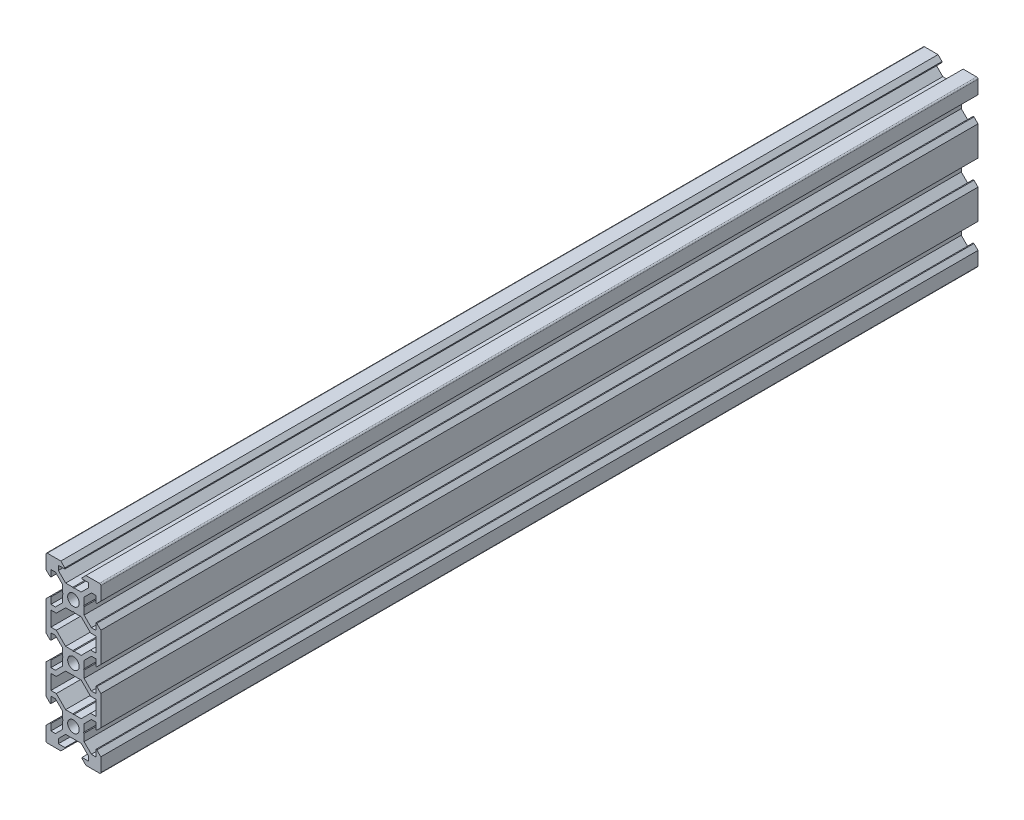
SolidWorks part; units mm, degrees
ref_plane "Plan de face" through (0, 0, 0) normal (0, 0, 1) x (1, 0, 0)
ref_plane "Plan de dessus" through (0, 0, 0) normal (0, 1, 0) x (1, 0, 0)
ref_plane "Plan de droite" through (0, 0, 0) normal (1, 0, 0) x (0, 0, -1)
ref_axis "Axe" through (0, 0, -13.782) along (0, 0, 1)
sketch "Esquisse1" plane through (0, 0, 0) normal (0, 0, 1) x (1, 0, 0)
  line L0 (0, 27.6392) -> (0, -27.6392) construction
  line L1 (-33.6074, 0) -> (33.6074, 0) construction
  line L2 (0, 0) -> (-22.2114, 22.2114) construction
  line L3 (-9.5, 10) -> (-4.58, 10)
  line L4 (-4.58, 10) -> (-3.125, 8.545)
  line L5 (-3.125, 8.545) -> (-3.125, 8.2)
  line L6 (-3.125, 8.2) -> (-5.5, 8.2)
  line L7 (-2.8393, 3.9) -> (-5.5, 6.5607)
  line L8 (-2.8393, 3.9) -> (-0.21, 3.9)
  line L9 (-5.5, 6.5607) -> (-5.5, 8.2)
  line L10 (0, 3.69) -> (0, 2.1)
  line L11 (-3.9, 2.8393) -> (-6.5607, 5.5)
  line L12 (-8.545, 3.125) -> (-8.2, 3.125)
  line L13 (-8.2, 3.125) -> (-8.2, 5.5)
  line L14 (-6.5607, 5.5) -> (-8.2, 5.5)
  line L15 (-10, 4.58) -> (-8.545, 3.125)
  line L16 (-10, 9.5) -> (-10, 4.58)
  line L17 (-0.21, 3.9) -> (0, 3.69)
  line L18 (-3.9, 2.8393) -> (-3.9, 0.21)
  line L19 (-6.2393, -12.7) -> (-8.2, -12.7)
  line L20 (-3.9, 0.21) -> (-3.69, 0)
  line L21 (-0.21, -3.9) -> (0, -3.69)
  line L22 (0, -3.69) -> (0, -2.1)
  line L23 (-6.5607, -5.5) -> (-8.2, -5.5)
  line L24 (-2.8393, -3.9) -> (-0.21, -3.9)
  line L25 (-8.545, -3.125) -> (-8.2, -3.125)
  line L26 (-10, -4.58) -> (-8.545, -3.125)
  line L27 (-8.2, -3.125) -> (-8.2, -5.5)
  line L28 (-2.8393, -3.9) -> (-6.2393, -7.3)
  line L29 (-3.9, -2.8393) -> (-6.5607, -5.5)
  line L30 (-3.9, -2.8393) -> (-3.9, -0.21)
  line L31 (-3.9, -0.21) -> (-3.69, 0)
  line L32 (-6.2393, -7.3) -> (-8.2, -7.3)
  line L33 (-8.2, -7.3) -> (-8.2, -12.7)
  line L34 (-8.2, -10) -> (-10, -10) construction
  line L35 (-10, -15.42) -> (-10, -4.58)
  line L36 (-3.9, -19.79) -> (-3.69, -20)
  line L37 (-3.9, -17.1607) -> (-3.9, -19.79)
  line L38 (-3.9, -17.1607) -> (-6.5607, -14.5)
  line L39 (-2.8393, -16.1) -> (-6.2393, -12.7)
  line L40 (-8.2, -16.875) -> (-8.2, -14.5)
  line L41 (-10, -15.42) -> (-8.545, -16.875)
  line L42 (-8.545, -16.875) -> (-8.2, -16.875)
  line L43 (-2.8393, -16.1) -> (-0.21, -16.1)
  line L44 (-6.5607, -14.5) -> (-8.2, -14.5)
  line L45 (0, -16.31) -> (0, -17.9)
  line L46 (-0.21, -16.1) -> (0, -16.31)
  line L47 (-8.2, -30) -> (-10, -30) construction
  line L48 (-3.69, -20) -> (0, -20) construction
  line L49 (-0.21, -23.9) -> (0, -23.69)
  line L50 (0, -23.69) -> (0, -22.1)
  line L51 (-6.5607, -25.5) -> (-8.2, -25.5)
  line L52 (-2.8393, -23.9) -> (-0.21, -23.9)
  line L53 (-8.545, -23.125) -> (-8.2, -23.125)
  line L54 (-10, -24.58) -> (-8.545, -23.125)
  line L55 (-8.2, -23.125) -> (-8.2, -25.5)
  line L56 (-2.8393, -23.9) -> (-6.2393, -27.3)
  line L57 (-3.9, -22.8393) -> (-6.5607, -25.5)
  line L58 (-3.9, -22.8393) -> (-3.9, -20.21)
  line L59 (-3.9, -20.21) -> (-3.69, -20)
  line L60 (-10, -24.58) -> (-10, -35.42)
  line L61 (-8.2, -32.7) -> (-8.2, -27.3)
  line L62 (-6.2393, -32.7) -> (-8.2, -32.7)
  line L63 (-3.9, -39.79) -> (-3.69, -40)
  line L64 (-3.9, -37.1607) -> (-3.9, -39.79)
  line L65 (-3.9, -37.1607) -> (-6.5607, -34.5)
  line L66 (-2.8393, -36.1) -> (-6.2393, -32.7)
  line L67 (-8.2, -36.875) -> (-8.2, -34.5)
  line L68 (-10, -35.42) -> (-8.545, -36.875)
  line L69 (-8.545, -36.875) -> (-8.2, -36.875)
  line L70 (-2.8393, -36.1) -> (-0.21, -36.1)
  line L71 (-6.5607, -34.5) -> (-8.2, -34.5)
  line L72 (0, -36.31) -> (0, -37.9)
  line L73 (-0.21, -36.1) -> (0, -36.31)
  line L74 (-3.9, -40.21) -> (-3.69, -40)
  line L75 (-6.2393, -27.3) -> (-8.2, -27.3)
  line L76 (-3.9, -42.8393) -> (-3.9, -40.21)
  line L77 (-0.21, -43.9) -> (0, -43.69)
  line L78 (-10, -49.5) -> (-10, -44.58)
  line L79 (-10, -44.58) -> (-8.545, -43.125)
  line L80 (-6.5607, -45.5) -> (-8.2, -45.5)
  line L81 (-8.2, -43.125) -> (-8.2, -45.5)
  line L82 (-8.545, -43.125) -> (-8.2, -43.125)
  line L83 (-3.9, -42.8393) -> (-6.5607, -45.5)
  line L84 (0, -43.69) -> (0, -42.1)
  line L85 (-5.5, -46.5607) -> (-5.5, -48.2)
  line L86 (-2.8393, -43.9) -> (-0.21, -43.9)
  line L87 (-2.8393, -43.9) -> (-5.5, -46.5607)
  line L88 (-3.125, -48.2) -> (-5.5, -48.2)
  line L89 (-3.125, -48.545) -> (-3.125, -48.2)
  line L90 (-4.58, -50) -> (-3.125, -48.545)
  line L91 (-9.5, -50) -> (-4.58, -50)
  arc A0 (0, -2.1) -> (0, 2.1) centre (0, 0) cw
  arc A1 (-9.5, 10) -> (-10, 9.5) centre (-9.5, 9.5) ccw
  arc A2 (0, -37.9) -> (0, -42.1) centre (0, -40) ccw
  arc A3 (-9.5, -50) -> (-10, -49.5) centre (-9.5, -49.5) cw
  arc A4 (0, -17.9) -> (0, -22.1) centre (0, -20) ccw
  point P4 (0, 0)
  point P7 (0, 0)
  point P30 (-10, 10)
  point P60 (0, -20)
  point P111 (-10, -50)
  dimension "D5" = 11
  dimension "D2" = 2.1
  dimension "D3" = 6.25
  dimension "D10" = 0.5
  dimension "D4" = 9.16
  dimension "D6" = 1.5
  dimension "D7" = 1.8
  dimension "D8" = 4.3
  dimension "D9" = 20
  dimension "D11" = 0.42
  dimension "D12" = 10
  dimension "D13" = 1.8
extrude "Boss.-Extru.1" add sketch "Esquisse1" along normal blind 320
sketch "Esquisse3" plane through (0, 0, 320) normal (0, 0, 1) x (1, 0, 0)
  line L0 (0, 0) -> (-9.8536, 9.8536) construction
  line L1 (-8.2, 8.2) -> (-8.2, 6.57)
  line L2 (-8.2, 6.57) -> (-7.54, 6.57)
  line L3 (-7.54, 6.57) -> (-6.57, 7.54)
  line L4 (-8.2, 3.125) -> (-8.2, 5.5) construction
  line L5 (-6.57, 8.2) -> (-6.57, 7.54)
  line L6 (-8.2, 8.2) -> (-6.57, 8.2)
  line L7 (-5.5, 6.5607) -> (-5.5, 8.2) construction
  line L8 (-3.69, -20) -> (0, -20) construction
  line L9 (-8.2, -48.2) -> (-6.57, -48.2)
  line L10 (-6.57, -48.2) -> (-6.57, -47.54)
  line L11 (-7.54, -46.57) -> (-6.57, -47.54)
  line L12 (-8.2, -46.57) -> (-7.54, -46.57)
  line L13 (-8.2, -48.2) -> (-8.2, -46.57)
  arc A0 (-9.5, 10) -> (-10, 9.5) centre (-9.5, 9.5) ccw construction
  point P13 (-7.055, 7.055)
  point P14 (-6.57, 7.87)
  point P26 (-7.055, -47.055)
  dimension "D1" = 1.07
extrude "Enlèv. mat.-Extru.1" [suppressed] cut sketch "Esquisse3" against normal through all
mirror "Symétrie1" about plane through (0, 3.69, 320) normal (-1, 0, 0) of "Enlèv. mat.-Extru.1", "Boss.-Extru.1"
